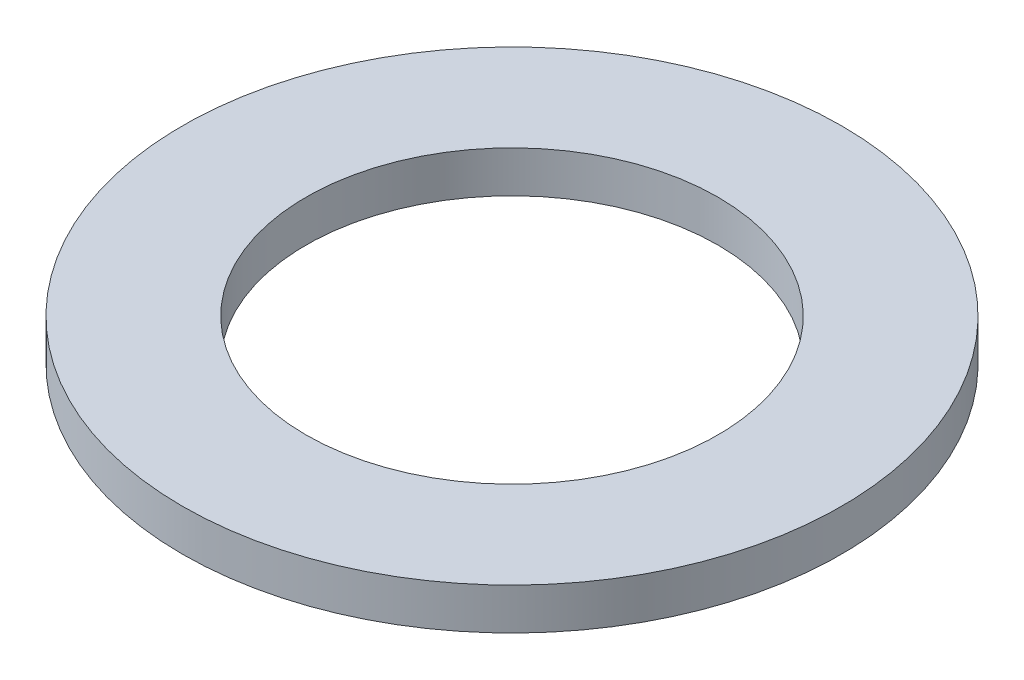
SolidWorks part; units mm, degrees
material "Alum Plate"
ref_plane "Front Plane" through (0, 0, 0) normal (0, 0, 1) x (1, 0, 0)
ref_plane "Top Plane" through (0, 0, 0) normal (0, 1, 0) x (1, 0, 0)
ref_plane "Right Plane" through (0, 0, 0) normal (1, 0, 0) x (0, 0, -1)
other "Bounding Box"
ref_plane "Default Plane" through (-8.9266, -12.7485, 0) normal (-0.1736, 0.9848, 0) x (0.9848, 0.1736, 0)
sketch "Sketch1" plane through (0, 0, 0) normal (0, 1, 0) x (1, 0, 0)
  circle A0 centre (0, 0) radius 7.9375
  circle A1 centre (0, 0) radius 12.7
  dimension "D1" = 15.875
  dimension "D2" = 25.4
extrude "Boss-Extrude1" add sketch "Sketch1" along normal mid plane 1.6002
